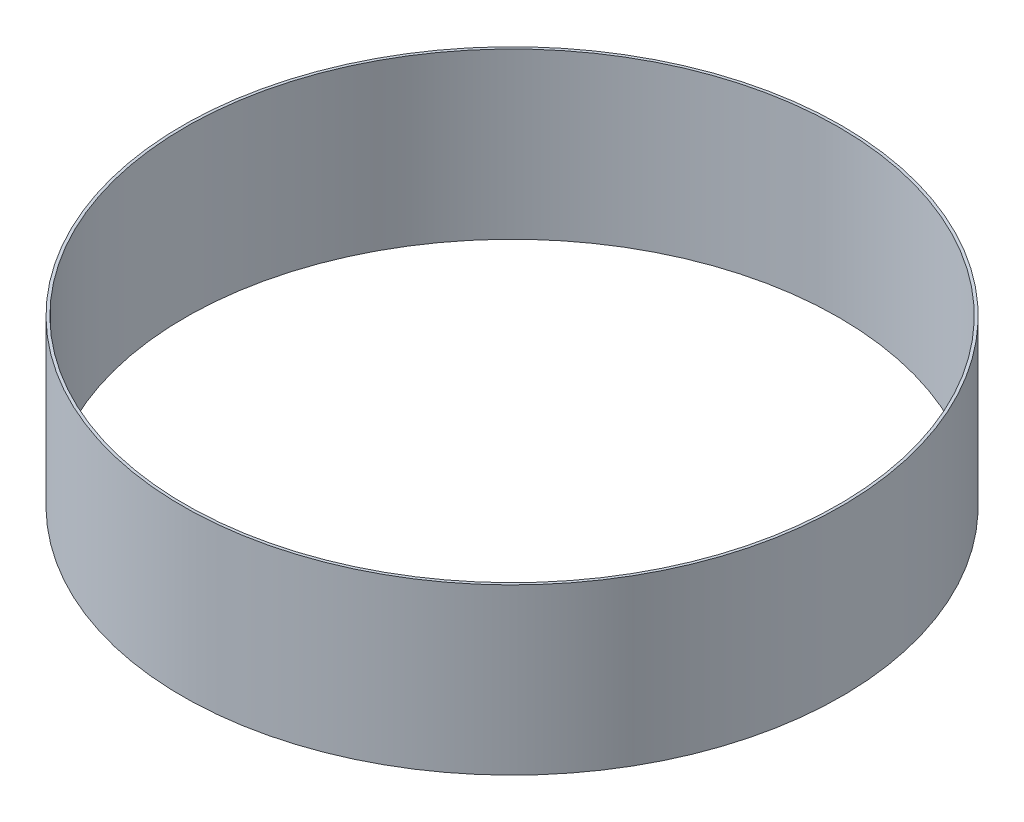
SolidWorks part; units mm, degrees
ref_plane "Front Plane" through (0, 0, 0) normal (0, 0, 1) x (1, 0, 0)
ref_plane "Top Plane" through (0, 0, 0) normal (0, 1, 0) x (1, 0, 0)
ref_plane "Right Plane" through (0, 0, 0) normal (1, 0, 0) x (0, 0, -1)
sketch "Sketch2" plane through (0, 0, 0) normal (0, 1, 0) x (1, 0, 0)
  circle A0 centre (0, 0) radius 151.13
  circle A1 centre (0, 0) radius 152.4
  dimension "D1" = 152.4
  dimension "D2" = 151.13
extrude "Boss-Extrude1" add sketch "Sketch2" along normal blind 76.2
